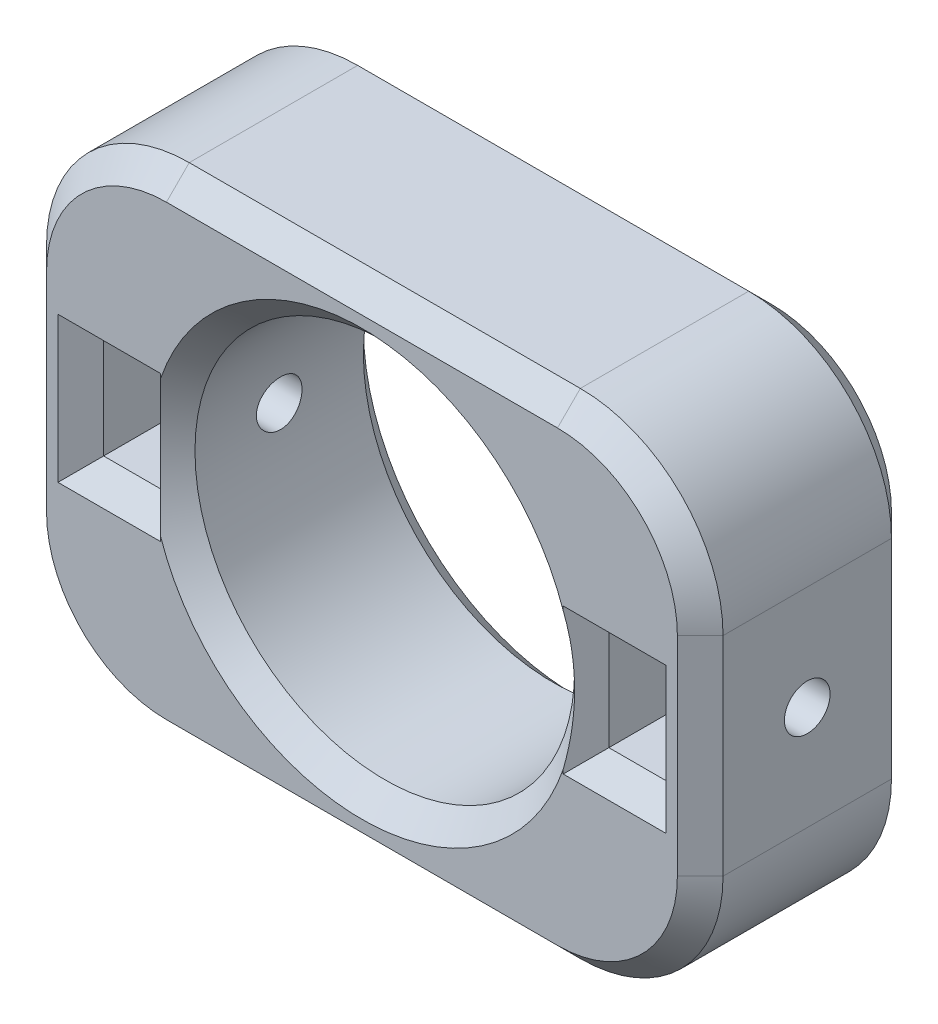
SolidWorks part; units mm, degrees
ref_plane "Front Plane" through (0, 0, 0) normal (0, 0, 1) x (1, 0, 0)
ref_plane "Top Plane" through (0, 0, 0) normal (0, 1, 0) x (1, 0, 0)
ref_plane "Right Plane" through (0, 0, 0) normal (1, 0, 0) x (0, 0, -1)
sketch "Sketch1" plane through (0, 0, 0) normal (0, 0, 1) x (1, 0, 0)
  line L1 (-23.7, -17.3) -> (23.7, -17.3)
  line L2 (-23.7, -17.3) -> (-23.7, 17.3)
  line L3 (-23.7, 17.3) -> (23.7, 17.3)
  line L4 (23.7, -17.3) -> (23.7, 17.3)
  line L5 (0, 17.3) -> (0, -17.3) construction
  line L6 (-23.7, 0) -> (23.7, 0) construction
  line L7 (15.7, -3.5) -> (19.7, -3.5) construction
  line L8 (15.7, -3.5) -> (15.7, 3.5) construction
  line L9 (15.7, 3.5) -> (19.7, 3.5) construction
  line L10 (19.7, -3.5) -> (19.7, 3.5) construction
  line L11 (17.7, 3.5) -> (17.7, -3.5) construction
  line L12 (15.7, 0) -> (19.7, 0) construction
  circle A0 centre (0, 0) radius 13.3
  circle A1 centre (0, 0) radius 17.3 construction
  point P8 (17.7, 0)
  point P17 (13.3, 0)
  dimension "D1" = 26.6
  dimension "D3" = 4
  dimension "D4" = 7
  dimension "D5" = 4
  dimension "D6" = 2.4
  dimension "D2" = 4
extrude "Boss-Extrude1" add sketch "Sketch1" along normal blind 15
sketch "Sketch2" plane through (23.7, 0, 0) normal (1, 0, 0) x (0, 0, -1)
  line L1 (-2, -3.5) -> (-13, -3.5) construction
  line L2 (-2, -3.5) -> (-2, 3.5) construction
  line L3 (-2, 3.5) -> (-13, 3.5) construction
  line L4 (-13, -3.5) -> (-13, 3.5) construction
  line L5 (-7.5, 3.5) -> (-7.5, -3.5) construction
  line L6 (-2, 0) -> (-13, 0) construction
  line L7 (-15, 17.3) -> (0, 17.3) construction
  circle A0 centre (-7.5, 0) radius 1.6
  point P0 (-7.5, 0)
  point P4 (0, 0)
  point P7 (-7.5, 17.3)
  dimension "D2" = 3.2
  dimension "D1" = 11
extrude "Cut-Extrude1" cut sketch "Sketch2" against normal through all
sketch "Sketch3" plane through (0, 0, 15) normal (0, 0, 1) x (1, 0, 0)
  line L0 (0, 17.3) -> (0, -17.3) construction
  line L1 (15.7, -3.5) -> (19.7, -3.5)
  line L2 (15.7, -3.5) -> (15.7, 3.5)
  line L3 (15.7, 3.5) -> (19.7, 3.5)
  line L4 (19.7, -3.5) -> (19.7, 3.5)
  line L5 (17.7, 3.5) -> (17.7, -3.5) construction
  line L6 (15.7, 0) -> (19.7, 0) construction
  line L7 (0, 17.3) -> (0, -17.3) construction
  line L8 (-15.7, 3.5) -> (-19.7, 3.5)
  line L9 (-19.7, -3.5) -> (-19.7, 3.5)
  line L10 (-15.7, -3.5) -> (-19.7, -3.5)
  line L11 (-15.7, -3.5) -> (-15.7, 3.5)
  point P0 (17.7, 0)
extrude "Cut-Extrude2" cut sketch "Sketch3" against normal up to vertex (13 mm away) up to point (23.7, 0, 2)
chamfer "Chamfer1" distance 1.6 angle 45 1 edges at (13.3, 0, 15)
chamfer "Chamfer2" distance 1.6 angle 45 8 edges at (17.7, 3.5, 15) (19.7, 0, 15) (17.7, -3.5, 15) (15.7, 0, 15) (-19.7, 0, 15) (-17.7, -3.5, 15) (-15.7, 0, 15) (-17.7, 3.5, 15)
fillet "Fillet1" radius 10 4 edges at (23.7, 17.3, 7.5) (23.7, -17.3, 7.5) (-23.7, -17.3, 7.5) (-23.7, 17.3, 7.5)
chamfer "Chamfer3" distance 1.6 angle 45 9 edges at (13.3, 0, 0) (-20.7711, 14.3711, 0) (-23.7, 0, 0) (-20.7711, -14.3711, 0) (0, -17.3, 0) (20.7711, -14.3711, 0) (23.7, 0, 0) (20.7711, 14.3711, 0) (0, 17.3, 0)
chamfer "Chamfer4" distance 1.6 angle 45 8 edges at (0, -17.3, 15) (20.7711, -14.3711, 15) (-20.7711, -14.3711, 15) (23.7, 0, 15) (-23.7, 0, 15) (20.7711, 14.3711, 15) (-20.7711, 14.3711, 15) (0, 17.3, 15)
